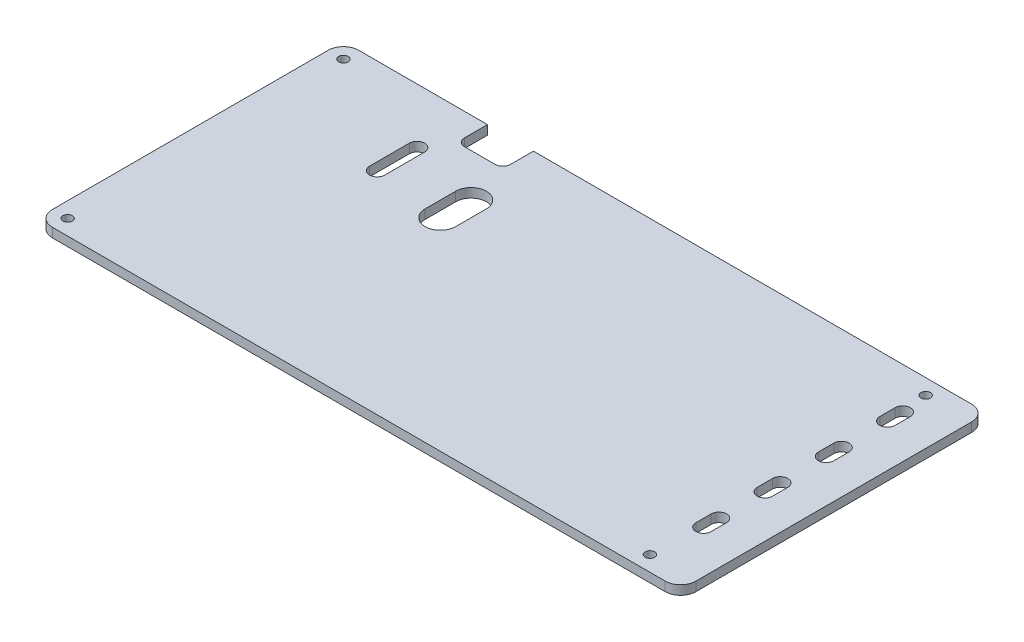
SolidWorks part; units mm, degrees
ref_plane "Front Plane" through (0, 0, 0) normal (0, 0, 1) x (1, 0, 0)
ref_plane "Top Plane" through (0, 0, 0) normal (0, 1, 0) x (1, 0, 0)
ref_plane "Right Plane" through (0, 0, 0) normal (1, 0, 0) x (0, 0, -1)
sketch "Sketch1" plane through (0, 0, 0) normal (0, 1, 0) x (1, 0, 0)
  line L1 (-105, 50) -> (105, 50)
  line L2 (-105, 50) -> (-105, -50)
  line L3 (-105, -50) -> (105, -50)
  line L4 (105, 50) -> (105, -50)
  line L5 (-105, 50) -> (105, -50) construction
  line L6 (-105, -50) -> (105, 50) construction
  point P0 (0, 0)
  dimension "D1" = 210
  dimension "D2" = 100
extrude "Boss-Extrude1" add sketch "Sketch1" along normal blind 3 contours L1 L4 L3 L2
sketch "Sketch2" plane through (0, 3, 0) normal (0, 1, 0) x (1, 0, 0)
  line L0 (-105, 50) -> (105, 50) construction
  line L1 (-105, 50) -> (-105, -50) construction
  line L2 (-105, -50) -> (105, -50) construction
  line L3 (105, 50) -> (105, -50) construction
  circle A0 centre (-100, 45) radius 1.55
  circle A1 centre (-100, -45) radius 1.55
  circle A2 centre (90, 45) radius 1.55
  circle A3 centre (90, -45) radius 1.55
  dimension "D3" = 3.1
  dimension "D4" = 3.1
  dimension "D5" = 3.1
  dimension "D6" = 3.1
  dimension "D1" = 5
  dimension "D2" = 5
  dimension "D7" = 5
  dimension "D8" = 5
  dimension "D9" = 5
  dimension "D10" = 15
  dimension "D11" = 15
  dimension "D12" = 5
extrude "Cut-Extrude1" cut sketch "Sketch2" against normal through all
fillet "Fillet1" radius 5 4 edges at (-105, 1.5, -50) (105, 1.5, -50) (105, 1.5, 50) (-105, 1.5, 50)
sketch "Sketch3" plane through (0, 3, 0) normal (0, 1, 0) x (1, 0, 0)
  line L0 (91, 50) -> (91, -50) construction
  line L5 (-100, 50) -> (100, 50) construction
  line L6 (-100, -50) -> (100, -50) construction
  line L7 (91, 36.5) -> (91, 31.5) construction
  line L12 (-63, 32) -> (-63, 19) construction
  line L13 (-60.5, 32) -> (-60.5, 19)
  line L18 (-39.365, 26) -> (-39.365, 16) construction
  line L19 (-34.365, 26) -> (-34.365, 16)
  line L20 (-65.5, 32) -> (-65.5, 19)
  line L21 (-105, 45) -> (-105, -45) construction
  line L22 (-44.365, 26) -> (-44.365, 16)
  line L23 (-58, 40) -> (-43, 40)
  line L24 (-58, 40) -> (-58, 50)
  line L25 (-58, 50) -> (-43, 50)
  line L26 (-43, 40) -> (-43, 50)
  line L27 (-58, 40) -> (-43, 50) construction
  line L28 (-58, 50) -> (-43, 40) construction
  line L29 (93.5, 36.5) -> (93.5, 31.5)
  line L30 (88.5, 36.5) -> (88.5, 31.5)
  line L31 (91, 16.5) -> (91, 11.5) construction
  line L32 (93.5, 16.5) -> (93.5, 11.5)
  line L33 (88.5, 16.5) -> (88.5, 11.5)
  line L34 (91, -3.5) -> (91, -8.5) construction
  line L35 (93.5, -3.5) -> (93.5, -8.5)
  line L36 (88.5, -3.5) -> (88.5, -8.5)
  line L37 (91, -23.5) -> (91, -28.5) construction
  line L38 (93.5, -23.5) -> (93.5, -28.5)
  line L39 (88.5, -23.5) -> (88.5, -28.5)
  arc A2 (-60.5, 32) -> (-65.5, 32) centre (-63, 32) ccw
  arc A3 (-65.5, 19) -> (-60.5, 19) centre (-63, 19) ccw
  arc A4 (-34.365, 26) -> (-44.365, 26) centre (-39.365, 26) ccw
  arc A5 (-44.365, 16) -> (-34.365, 16) centre (-39.365, 16) ccw
  arc A6 (93.5, 36.5) -> (88.5, 36.5) centre (91, 36.5) ccw
  arc A7 (88.5, 31.5) -> (93.5, 31.5) centre (91, 31.5) ccw
  arc A8 (93.5, 16.5) -> (88.5, 16.5) centre (91, 16.5) ccw
  arc A9 (88.5, 11.5) -> (93.5, 11.5) centre (91, 11.5) ccw
  arc A10 (93.5, -3.5) -> (88.5, -3.5) centre (91, -3.5) ccw
  arc A11 (88.5, -8.5) -> (93.5, -8.5) centre (91, -8.5) ccw
  arc A12 (93.5, -23.5) -> (88.5, -23.5) centre (91, -23.5) ccw
  arc A13 (88.5, -28.5) -> (93.5, -28.5) centre (91, -28.5) ccw
  point P4 (91, 34)
  point P12 (-63, 25.5)
  point P17 (-39.365, 21)
  point P26 (-50.5, 45)
  point P35 (91, 14)
  point P42 (91, -6)
  point P49 (91, -26)
  dimension "D2" = 196
  dimension "D3" = 5
  dimension "D4" = 42
  dimension "D5" = 75.5
  dimension "D6" = 5
  dimension "D7" = 13
  dimension "D8" = 65.635
  dimension "D9" = 71
  dimension "D10" = 10
  dimension "D11" = 10
  dimension "D12" = 10
  dimension "D13" = 54.5
  dimension "D14" = 15
  dimension "D15" = 5
  dimension "D16" = 5
  dimension "D17" = 5
  dimension "D18" = 24
  dimension "D19" = 44
  dimension "D20" = 64
  dimension "D21" = 84
  dimension "D22" = 5
  dimension "D23" = 5
  dimension "D24" = 5
  dimension "D25" = 5
extrude "Cut-Extrude2" cut sketch "Sketch3" against normal through all
fillet "Fillet2" radius 2.5 2 edges at (-43, 1.5, -40) (-58, 1.5, -40)
